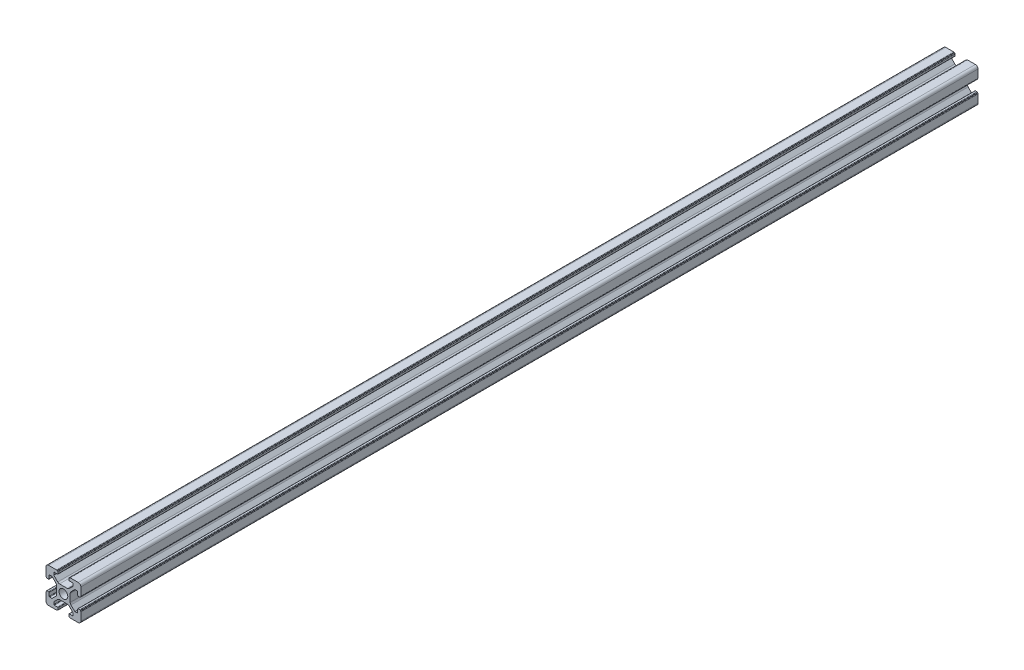
SolidWorks part; units mm, degrees
material "1060 Alloy"
ref_plane "Front Plane" through (0, 0, 0) normal (0, 0, 1) x (1, 0, 0)
ref_plane "Top Plane" through (0, 0, 0) normal (0, 1, 0) x (1, 0, 0)
ref_plane "Right Plane" through (0, 0, 0) normal (1, 0, 0) x (0, 0, -1)
sketch "Sketch1" plane through (0, 0, 0) normal (0, 0, 1) x (1, 0, 0)
  line L0 (3.8995, 3.9005) -> (10.4604, 10.4604) construction
  line L2 (-3.9002, 2.2177) -> (-3.9002, -2.2208)
  line L5 (-3.9005, 3.899) -> (3.9001, -3.8986) construction
  line L6 (-3.9, -3.901) -> (3.8995, 3.9005) construction
  line L7 (-0.0002, 10) -> (-0.0002, -9.9996) construction
  line L8 (-0.0002, -9.9996) -> (-0.0002, 10) construction
  line L9 (5.5006, 6.5619) -> (3.2793, 4.3405)
  line L14 (-10.0002, 9.9996) -> (9.9994, -10) construction
  line L15 (-9.9999, -10.0001) -> (9.9998, 10) construction
  line L16 (6.5613, 5.5012) -> (4.3401, 3.28)
  line L17 (-5.5002, 6.5603) -> (-3.279, 4.3391)
  line L18 (-6.5609, 5.4996) -> (-4.3395, 3.2783)
  line L19 (7.9206, 5.5012) -> (6.5613, 5.5012)
  line L20 (8.2006, 3.3812) -> (8.2006, 5.2212)
  line L21 (9.4206, 3.1012) -> (8.4806, 3.1012)
  line L22 (9.7006, 3.6012) -> (9.7006, 3.3812)
  line L23 (-8.5002, 9.9996) -> (-3.8802, 9.9996)
  line L24 (-3.6002, 9.7196) -> (-3.6002, 9.6996)
  line L25 (-3.6002, 9.6996) -> (-3.3802, 9.6996)
  line L26 (-3.1002, 9.4196) -> (-3.1002, 8.4796)
  line L27 (-3.3802, 8.1996) -> (-5.2202, 8.1996)
  line L28 (-5.5002, 7.9196) -> (-5.5002, 6.5603)
  line L29 (-7.9202, 5.4996) -> (-6.5609, 5.4996)
  line L30 (-8.2002, 3.3796) -> (-8.2002, 5.2196)
  line L31 (-9.4202, 3.0996) -> (-8.4802, 3.0996)
  line L32 (-9.7202, 3.5996) -> (-9.7002, 3.5996)
  line L33 (-9.7002, 3.5996) -> (-9.7002, 3.3796)
  line L34 (-10.0002, 8.4996) -> (-10.0002, 3.8796)
  line L35 (10.0006, 8.5012) -> (10.0006, 3.8812)
  line L36 (8.5006, 10.0012) -> (3.8806, 10.0012)
  line L37 (3.6006, 9.7012) -> (3.3806, 9.7012)
  line L38 (3.1006, 9.4212) -> (3.1006, 8.4812)
  line L39 (3.3806, 8.2012) -> (5.2206, 8.2012)
  line L40 (5.5006, 7.9212) -> (5.5006, 6.5619)
  line L41 (6.5629, -5.4996) -> (4.3415, -3.2783)
  line L42 (5.5022, -6.5603) -> (3.281, -4.3391)
  line L43 (5.5022, -7.9196) -> (5.5022, -6.5603)
  line L44 (3.3822, -8.1996) -> (5.2222, -8.1996)
  line L45 (3.1022, -9.4196) -> (3.1022, -8.4796)
  line L46 (3.6022, -9.6996) -> (3.3822, -9.6996)
  line L47 (8.5022, -9.9996) -> (3.8822, -9.9996)
  line L48 (10.0022, -8.4996) -> (10.0022, -3.8796)
  line L49 (9.7022, -3.5996) -> (9.7022, -3.3796)
  line L50 (9.4222, -3.0996) -> (8.4822, -3.0996)
  line L51 (8.2022, -3.3796) -> (8.2022, -5.2196)
  line L52 (7.9222, -5.4996) -> (6.5629, -5.4996)
  line L53 (-5.4986, -6.5619) -> (-3.2773, -4.3405)
  line L54 (-6.5593, -5.5012) -> (-4.3395, -3.2814)
  line L55 (-7.9186, -5.5012) -> (-6.5593, -5.5012)
  line L56 (-8.1986, -3.3812) -> (-8.1986, -5.2212)
  line L57 (-9.4186, -3.1012) -> (-8.4786, -3.1012)
  line L58 (-9.6986, -3.6012) -> (-9.6986, -3.3812)
  line L59 (-9.9986, -8.5012) -> (-9.9986, -3.8812)
  line L60 (-8.4986, -10.0012) -> (-3.8786, -10.0012)
  line L61 (-3.5986, -9.7012) -> (-3.3786, -9.7012)
  line L62 (-3.0986, -9.4212) -> (-3.0986, -8.4812)
  line L63 (-3.3786, -8.2012) -> (-5.2186, -8.2012)
  line L64 (-5.4986, -7.9212) -> (-5.4986, -6.5619)
  line L65 (-2.233, 3.8998) -> (2.2187, 3.9012)
  line L66 (3.9008, 2.234) -> (3.9022, -2.2177)
  line L67 (2.235, -3.8998) -> (-2.2167, -3.9012)
  line L68 (3.6006, 9.7212) -> (3.6006, 9.6996)
  line L69 (9.7006, 3.6012) -> (9.7206, 3.6012)
  line L70 (-9.6986, -3.6012) -> (-9.7186, -3.6012)
  line L71 (-3.5986, -9.7012) -> (-3.5986, -9.7212)
  line L72 (3.6022, -9.6996) -> (3.6022, -9.7196)
  line L73 (9.7222, -3.5996) -> (9.7022, -3.5996)
  arc A0 (-3.6002, 9.7196) -> (-3.8802, 9.9996) centre (-3.8802, 9.7196) ccw
  arc A1 (-3.3802, 9.6996) -> (-3.1002, 9.4196) centre (-3.3802, 9.4196) cw
  arc A2 (-3.1002, 8.4796) -> (-3.3802, 8.1996) centre (-3.3802, 8.4796) cw
  arc A3 (-10.0002, 8.4996) -> (-8.5002, 9.9996) centre (-8.5002, 8.4996) cw
  arc A4 (-8.2002, 3.3796) -> (-8.4802, 3.0996) centre (-8.4802, 3.3796) cw
  arc A5 (-9.4202, 3.0996) -> (-9.7002, 3.3796) centre (-9.4202, 3.3796) cw
  arc A6 (-9.7202, 3.5996) -> (-10.0002, 3.8796) centre (-9.7202, 3.8796) cw
  arc A7 (-3.279, 4.3391) -> (-2.233, 3.8998) centre (-2.2183, 5.3997) ccw
  arc A8 (-4.3395, 3.2783) -> (-3.9002, 2.2177) centre (-5.4002, 2.2177) cw
  arc A9 (-7.9202, 5.4996) -> (-8.2002, 5.2196) centre (-7.9202, 5.2196) ccw
  arc A10 (-5.2202, 8.1996) -> (-5.5002, 7.9196) centre (-5.2202, 7.9196) ccw
  arc A12 (-4.3395, -3.2814) -> (-3.9002, -2.2208) centre (-5.4002, -2.2208) ccw
  arc A13 (8.2006, 5.2212) -> (7.9206, 5.5012) centre (7.9206, 5.2212) ccw
  arc A14 (8.4806, 3.1012) -> (8.2006, 3.3812) centre (8.4806, 3.3812) cw
  arc A15 (9.7006, 3.3812) -> (9.4206, 3.1012) centre (9.4206, 3.3812) cw
  arc A16 (9.7206, 3.6012) -> (10.0006, 3.8812) centre (9.7206, 3.8812) ccw
  arc A17 (8.5006, 10.0012) -> (10.0006, 8.5012) centre (8.5006, 8.5012) cw
  arc A18 (3.6006, 9.7212) -> (3.8806, 10.0012) centre (3.8806, 9.7212) cw
  arc A19 (3.1006, 9.4212) -> (3.3806, 9.7012) centre (3.3806, 9.4212) cw
  arc A20 (3.3806, 8.2012) -> (3.1006, 8.4812) centre (3.3806, 8.4812) cw
  arc A21 (5.5006, 7.9212) -> (5.2206, 8.2012) centre (5.2206, 7.9212) ccw
  arc A22 (3.2793, 4.3405) -> (2.2187, 3.9012) centre (2.2187, 5.4012) cw
  arc A23 (4.3401, 3.28) -> (3.9008, 2.234) centre (5.4007, 2.2193) ccw
  arc A25 (5.2222, -8.1996) -> (5.5022, -7.9196) centre (5.2222, -7.9196) ccw
  arc A26 (3.1022, -8.4796) -> (3.3822, -8.1996) centre (3.3822, -8.4796) cw
  arc A27 (3.3822, -9.6996) -> (3.1022, -9.4196) centre (3.3822, -9.4196) cw
  arc A28 (3.6022, -9.7196) -> (3.8822, -9.9996) centre (3.8822, -9.7196) ccw
  arc A29 (10.0022, -8.4996) -> (8.5022, -9.9996) centre (8.5022, -8.4996) cw
  arc A30 (9.7222, -3.5996) -> (10.0022, -3.8796) centre (9.7222, -3.8796) cw
  arc A31 (9.4222, -3.0996) -> (9.7022, -3.3796) centre (9.4222, -3.3796) cw
  arc A32 (8.2022, -3.3796) -> (8.4822, -3.0996) centre (8.4822, -3.3796) cw
  arc A33 (7.9222, -5.4996) -> (8.2022, -5.2196) centre (7.9222, -5.2196) ccw
  arc A34 (4.3415, -3.2783) -> (3.9022, -2.2177) centre (5.4022, -2.2177) cw
  arc A35 (3.281, -4.3391) -> (2.235, -3.8998) centre (2.2203, -5.3997) ccw
  circle A36 centre (0.001, -0.001) radius 2.5 construction
  arc A37 (-8.1986, -5.2212) -> (-7.9186, -5.5012) centre (-7.9186, -5.2212) ccw
  arc A38 (-8.4786, -3.1012) -> (-8.1986, -3.3812) centre (-8.4786, -3.3812) cw
  arc A39 (-9.6986, -3.3812) -> (-9.4186, -3.1012) centre (-9.4186, -3.3812) cw
  arc A40 (-9.7186, -3.6012) -> (-9.9986, -3.8812) centre (-9.7186, -3.8812) ccw
  arc A41 (-8.4986, -10.0012) -> (-9.9986, -8.5012) centre (-8.4986, -8.5012) cw
  arc A42 (-3.5986, -9.7212) -> (-3.8786, -10.0012) centre (-3.8786, -9.7212) cw
  arc A43 (-3.0986, -9.4212) -> (-3.3786, -9.7012) centre (-3.3786, -9.4212) cw
  arc A44 (-3.3786, -8.2012) -> (-3.0986, -8.4812) centre (-3.3786, -8.4812) cw
  arc A45 (-5.4986, -7.9212) -> (-5.2186, -8.2012) centre (-5.2186, -7.9212) ccw
  arc A46 (-3.2773, -4.3405) -> (-2.2167, -3.9012) centre (-2.2167, -5.4012) cw
  arc A48 (-4.3381, -3.28) -> (-3.8988, -2.234) centre (-5.3987, -2.2193) ccw [skipped]
  point P0 (0, 0)
  point P9 (-0.0002, 0.0002)
  point P12 (-0.0003, -0.0003)
  point P43 (-3.6002, 9.9996)
  point P46 (-3.1002, 9.6996)
  point P49 (-3.1002, 8.1996)
  point P55 (-8.2002, 3.0996)
  point P58 (-9.7002, 3.0996)
  point P61 (-10.0002, 3.5996)
  point P64 (-2.8395, 3.8996)
  point P67 (-3.9002, 2.839)
  point P70 (-8.2002, 5.4996)
  point P73 (-5.5002, 8.1996)
  point P184 (0.001, 0)
  dimension "D14" = 0.28
  dimension "D15" = 0.28
  dimension "D16" = 0.28
  dimension "D17" = 1.5
  dimension "D18" = 0.28
  dimension "D19" = 1.5
  dimension "D20" = 1.5
  dimension "D21" = 0.28
  dimension "D23" = 5
  dimension "D27" = 1.5
  dimension "D1" = 7.8
  dimension "D2" = 7.8
  dimension "D3" = 3.1
  dimension "D4" = 3.6
  dimension "D5" = 20
  dimension "D6" = 20
  dimension "D7" = 0.75
  dimension "D8" = 1.8
  dimension "D9" = 5.5
  dimension "D10" = 6.4
  dimension "D11" = 6.4
  dimension "D12" = 3.7627
  dimension "D13" = 0.3
  dimension "D24" = 4.62
  dimension "D25" = 3.9005
  dimension "D26" = 7.801
  dimension "D22" = 4
extrude "Boss-Extrude1" add sketch "Sketch1" along normal blind 515 contours L53 A46 L67 A35 L42 L43 A25 L44 A26 L45 A27 L46 L72 A28 L47 A29 L48 A30 L73 L49 A31 L50 A32 L51 A33 L52 L41 A34 L66 A23 L16 L19 A13 L20 A14 L21 A15 L22 L69 A16 L35 A17 L36 A18 L68 L37 A19 L38 A20 region at (0.0009, 0, 0)
sketch3d "3DSketch2"
  circle A0 centre (0, 0, 0) radius 2.5
  point P2 (0, 0, 2.5)
extrude "Cut-Extrude1" cut sketch "3DSketch2" along direction (0, 0, 1) on the side of the normal through all contours A0
